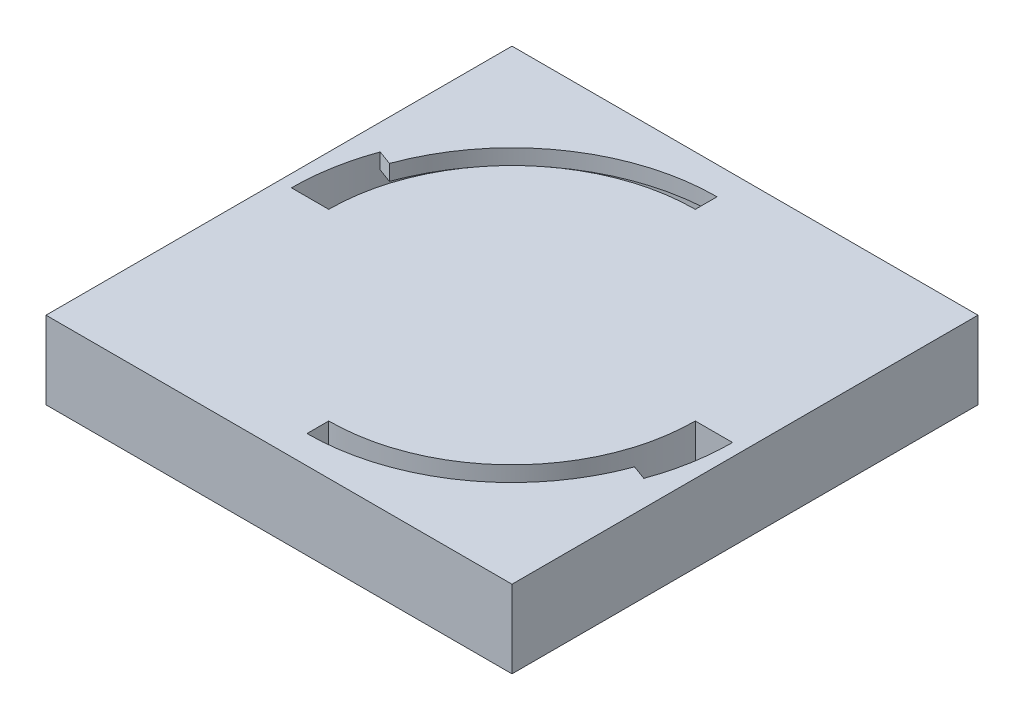
SolidWorks part; units mm, degrees
ref_plane "Front Plane" through (0, 0, 0) normal (0, 0, 1) x (1, 0, 0)
ref_plane "Top Plane" through (0, 0, 0) normal (0, 1, 0) x (1, 0, 0)
ref_plane "Right Plane" through (0, 0, 0) normal (1, 0, 0) x (0, 0, -1)
sketch "Sketch1" plane through (0, 0, 0) normal (0, 1, 0) x (1, 0, 0)
  line L1 (0, 0) -> (30, 0)
  line L2 (0, 0) -> (0, 30)
  line L3 (0, 30) -> (30, 30)
  line L4 (30, 0) -> (30, 30)
  dimension "D1" = 30
  dimension "D2" = 30
extrude "Boss-Extrude1" add sketch "Sketch1" along normal blind 5
ref_plane "Plane1" through (0, 0, -15) normal (0, 0, 1) x (1, 0, 0)
sketch "Sketch2" plane through (0, 0, -15) normal (0, 0, 1) x (1, 0, 0)
  line L0 (0.8, 4) -> (0.8, 2)
  line L1 (0, 5) -> (30, 5) construction
  line L2 (0.8, 2) -> (3.2, 2)
  line L5 (1.8, 5) -> (1.8, 4)
  line L6 (1.8, 4) -> (0.8, 4)
  line L7 (29.2, 2) -> (29.2, 5)
  line L8 (3.2, 5) -> (3.2, 2)
  line L9 (0, 5) -> (0, 0) construction
  line L14 (15, 5) -> (15, 0)
  line L15 (0, 0) -> (30, 0) construction
  line L16 (26.8, 5) -> (29.2, 5)
  line L17 (26.8, 5) -> (26.8, 2)
  line L18 (28.2, 4) -> (29.2, 4)
  line L19 (28.2, 5) -> (28.2, 4)
  line L20 (29.2, 2) -> (26.8, 2)
  line L21 (29.2, 4) -> (29.2, 2)
  line L27 (3.2, 5) -> (0.8, 5)
  line L28 (0.8, 2) -> (0.8, 5)
  point P22 (0, 0)
  dimension "D1" = 3
  dimension "D2" = 1
  dimension "D3" = 1
  dimension "D4" = 1.4
  dimension "D6" = 3.2
revolve "Cut-Revolve2" cut sketch "Sketch2" angle 90 about L14 region at (2.1129, 3.3387, -15) region at (27.8871, 3.3387, -15)
revolve "Cut-Revolve3" cut sketch "Sketch2<5>" angle 20 about L14 region at (2.1129, 3.3387, -15) region at (1.3, 4.5, -15) region at (28.7, 4.5, -15)
sketch "Sketch2<5>" plane through (0, 0, -15) normal (0, 0, 1) x (1, 0, 0) same geometry as "Sketch2"
